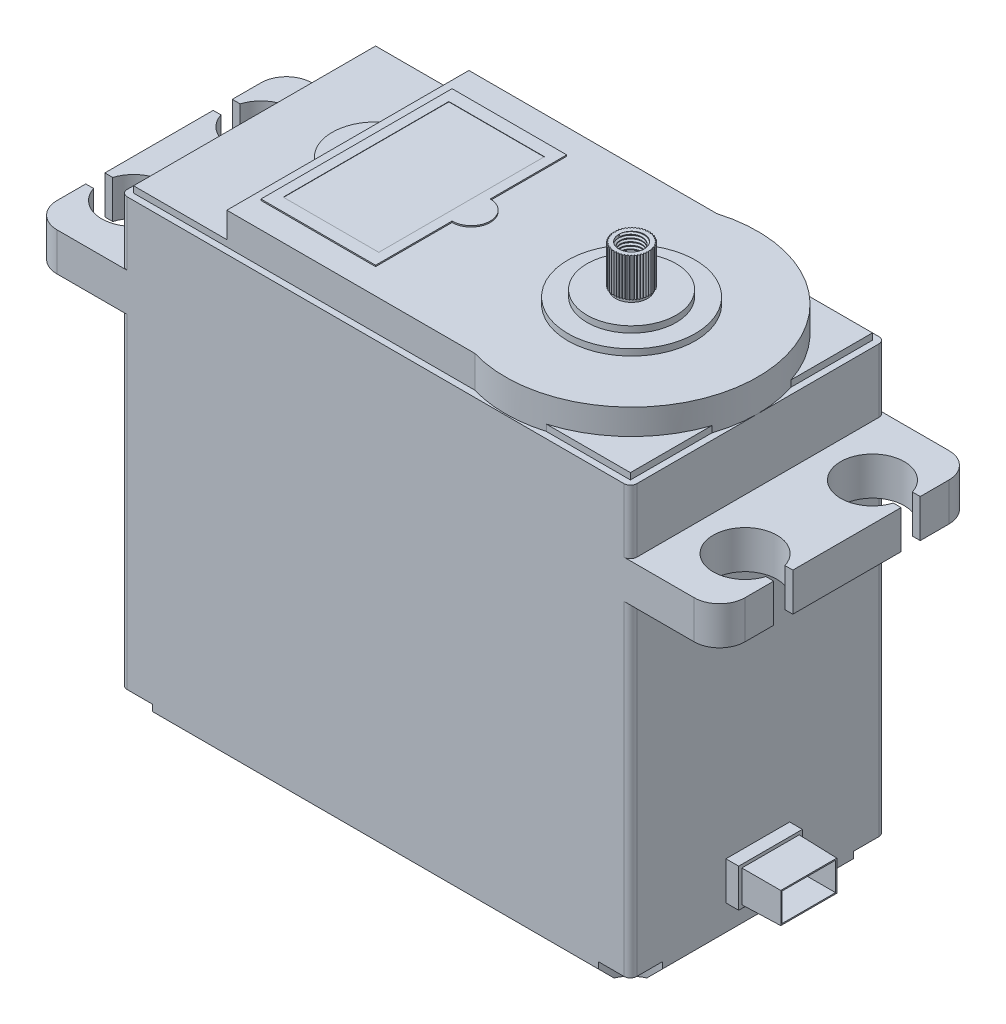
SolidWorks part; units mm, degrees
note: The reader was unsure of these and kept them because the rebuilt part matched: shared geometry of "Sketch11<4>", "Sketch11<5>", "Sketch11<6>".
material "ABS"
ref_plane "Front Plane" through (0, 0, 0) normal (0, 0, 1) x (1, 0, 0)
ref_plane "Top Plane" through (0, 0, 0) normal (0, 1, 0) x (1, 0, 0)
ref_plane "Right Plane" through (0, 0, 0) normal (1, 0, 0) x (0, 0, -1)
sketch "Sketch1" plane through (0, 0, 0) normal (0, 1, 0) x (1, 0, 0)
  line L1 (-20, -10) -> (20, -10)
  line L2 (-20, -10) -> (-20, 10)
  line L3 (-20, 10) -> (20, 10)
  line L4 (20, -10) -> (20, 10)
  line L5 (-20, -10) -> (20, 10) construction
  line L6 (-20, 10) -> (20, -10) construction
  point P0 (0, 0)
  dimension "D1" = 40
  dimension "D2" = 20
extrude "Boss-Extrude1" add sketch "Sketch1" along normal blind 35
sketch "Sketch2" plane through (20, 0, 0) normal (1, 0, 0) x (0, 0, -1)
  line L0 (-10, 35) -> (-10, 0) construction
  line L1 (-10, 30) -> (10, 30)
  line L2 (-10, 30) -> (-10, 27)
  line L3 (-10, 27) -> (10, 27)
  line L4 (10, 30) -> (10, 27)
  line L5 (10, 35) -> (10, 0) construction
  line L6 (-10, 35) -> (10, 35) construction
  dimension "D1" = 5
  dimension "D2" = 3
extrude "Boss-Extrude2" add sketch "Sketch2" along normal blind 7
sketch "Sketch3" plane through (0, 30, 0) normal (0, 1, 0) x (1, 0, 0)
  line L0 (30.4327, 0) -> (4.9254, 0) construction
  line L1 (0, 13.3538) -> (0, -14.6292) construction
  line L2 (26.3848, 5.75) -> (27, 5.75)
  line L3 (27, 10) -> (27, -10) construction
  line L4 (27, 5.75) -> (27, 4.25)
  line L5 (27, 4.25) -> (26.3848, 4.25)
  line L6 (27, -4.25) -> (26.3848, -4.25)
  line L7 (27, -5.75) -> (27, -4.25)
  line L8 (26.3848, -5.75) -> (27, -5.75)
  line L9 (-26.3848, -5.75) -> (-27, -5.75)
  line L10 (-27, -5.75) -> (-27, -4.25)
  line L11 (-27, -4.25) -> (-26.3848, -4.25)
  line L12 (-27, 4.25) -> (-26.3848, 4.25)
  line L13 (-27, 5.75) -> (-27, 4.25)
  line L14 (-26.3848, 5.75) -> (-27, 5.75)
  circle A0 centre (24, 5) radius 2.5
  circle A1 centre (24, -5) radius 2.5
  circle A2 centre (-24, -5) radius 2.5
  circle A3 centre (-24, 5) radius 2.5
  point P15 (27, 5)
  line M4 (27, -10) -> (27, 10)
  dimension "D2" = 5
  dimension "D1" = 10
  dimension "D3" = 1.5
  dimension "D4" = 3
sketch "Sketch4" plane through (-20, 0, 0) normal (-1, 0, 0) x (0, 0, 1)
  line L0 (10, 35) -> (10, 0) construction
  line L1 (-10, 30) -> (10, 30)
  line L2 (-10, 30) -> (-10, 27)
  line L3 (-10, 27) -> (10, 27)
  line L4 (10, 30) -> (10, 27)
  dimension "D1" = 3
extrude "Boss-Extrude3" add sketch "Sketch4" along normal blind 7
extrude "Cut-Extrude1" cut sketch "Sketch3" against normal through all contours A2 | A1 | A0 | A3 | A2 L11 L10 L9 | L12 A3 L14 L13 | L6 A1 L8 M4 | A0 L5 L2 M4
sketch "Sketch5" plane through (20, 0, 0) normal (1, 0, 0) x (0, 0, -1)
  line L0 (-10, 0) -> (10, 0) construction
  line L1 (-2.5, 6) -> (2.5, 6)
  line L2 (-2.5, 6) -> (-2.5, 3)
  line L3 (-2.5, 3) -> (2.5, 3)
  line L4 (2.5, 6) -> (2.5, 3)
  point P6 (0, 3)
  dimension "D1" = 5
  dimension "D2" = 3
  dimension "D3" = 3
extrude "Boss-Extrude4" add sketch "Sketch5" along normal blind 1
sketch "Sketch6" plane through (21, 0, 0) normal (1, 0, 0) x (0, 0, -1)
  line L0 (-2.5, 3) -> (2.5, 3) construction
  line L1 (-2.25, 5.75) -> (2.25, 5.75)
  line L2 (-2.25, 5.75) -> (-2.25, 3.25)
  line L3 (-2.25, 3.25) -> (2.25, 3.25)
  line L4 (2.25, 5.75) -> (2.25, 3.25)
  line L5 (2.5, 3) -> (2.5, 6) construction
  line L6 (-2.05, 5.55) -> (2.05, 5.55)
  line L7 (2.05, 5.55) -> (2.05, 3.45)
  line L8 (-2.05, 3.45) -> (2.05, 3.45)
  line L9 (-2.05, 5.55) -> (-2.05, 3.45)
  point P4 (0, 3.25)
  point P7 (0, 3)
  point P8 (2.25, 4.5)
  point P11 (2.5, 4.5)
  dimension "D1" = 4.5
  dimension "D2" = 2.5
  dimension "D3" = 0.2
extrude "Boss-Extrude5" add sketch "Sketch6" along normal blind 3 draft 1
sketch "Sketch10" plane through (0, 35, 0) normal (0, 1, 0) x (1, 0, 0)
  line L0 (-20, -10) -> (20, -10) construction
  line L1 (-19.5, 9.5) -> (19.5, 9.5)
  line L2 (-19.5, 9.5) -> (-19.5, -9.5)
  line L3 (-19.5, -9.5) -> (19.5, -9.5)
  line L4 (19.5, 9.5) -> (19.5, -9.5)
  line L5 (20, -10) -> (20, 10) construction
  point P4 (0, -9.5)
  point P6 (19.5, 0)
  dimension "D1" = 0.5
  dimension "D2" = 0.5
extrude "Boss-Extrude6" add sketch "Sketch10" along normal blind 0.5
sketch "Sketch11" plane through (0, 35.5, 0) normal (0, 1, 0) x (1, 0, 0)
  line L1 (-19.5, -9.5) -> (19.5, -9.5) construction
  line L4 (-12.1768, -9.5) -> (7.2877, -9.5)
  line L6 (-12.1768, 9.5) -> (-12.1768, -9.5)
  line L7 (7.2877, 9.5) -> (-12.1768, 9.5)
  arc A0 (7.2877, -9.5) -> (7.2877, 9.5) centre (10.0941, 0) ccw
  arc A1 (-12.1768, 2.8483) -> (-12.1768, -2.5749) centre (-10.1595, 0.1367) ccw
  circle A2 centre (10.0941, 0) radius 5
  circle A3 centre (10.0941, 0) radius 3.5
  circle A4 centre (10.0941, 0) radius 1.1906
  line M2 (-19.5, -9.5) -> (19.5, -9.5)
  line M3 (19.5, -9.5) -> (19.5, 9.5)
  line M4 (19.5, 9.5) -> (-19.5, 9.5)
  dimension "D1" = 7
  dimension "D2" = 10
extrude "Boss-Extrude7" add sketch "Sketch11" along normal blind 2 contours A0 L6 A2 M2 M3 M4 | A3 | A2 A3 | A0 M2 | A0 M3 | A0 M4
extrude "Boss-Extrude8" add sketch "Sketch11<4>" along normal blind 1.8 contours L6 A1
sketch "Sketch11<4>" plane through (0, 35.5, 0) normal (0, 1, 0) x (1, 0, 0) same geometry as "Sketch11"
sketch "Sketch12" plane through (0, 35.5, 0) normal (0, -1, 0) x (1, 0, 0)
  line L0 (7.2877, 9.5) -> (12.9006, 9.5) construction
  line L1 (7.2877, 9.5) -> (12.9006, 9.5)
  arc A0 (12.9006, 9.5) -> (7.2877, 9.5) centre (10.0941, 0) ccw construction
  arc A1 (12.9006, 9.5) -> (7.2877, 9.5) centre (10.0941, 0) ccw
extrude "Boss-Extrude9" add sketch "Sketch12" along normal up to next
sketch "Sketch13" plane through (0, 35.5, 0) normal (0, -1, 0) x (1, 0, 0)
  line L0 (19.5, 3.1074) -> (19.5, -3.1074) construction
  line L1 (19.5, 3.1074) -> (19.5, -3.1074)
  arc A0 (19.5, -3.1074) -> (19.5, 3.1074) centre (10.0941, 0) ccw construction
  arc A1 (19.5, -3.1074) -> (19.5, 3.1074) centre (10.0941, 0) ccw
extrude "Boss-Extrude10" add sketch "Sketch13" along normal up to next
sketch "Sketch14" plane through (0, 35.5, 0) normal (0, -1, 0) x (1, 0, 0)
  line L0 (12.9006, -9.5) -> (7.2877, -9.5) construction
  line L1 (12.9006, -9.5) -> (7.2877, -9.5)
  arc A0 (7.2877, -9.5) -> (12.9006, -9.5) centre (10.0941, 0) ccw construction
  arc A1 (7.2877, -9.5) -> (12.9006, -9.5) centre (10.0941, 0) ccw
extrude "Boss-Extrude11" add sketch "Sketch14" along normal up to next
extrude "Boss-Extrude12" add sketch "Sketch11<5>" along normal blind 2.5 and the other way blind 10 contours A2 A3 | A3
sketch "Sketch11<5>" plane through (0, 35.5, 0) normal (0, 1, 0) x (1, 0, 0) same geometry as "Sketch11"
extrude "Boss-Extrude13" add sketch "Sketch11<6>" along normal blind 3 contours A3
sketch "Sketch11<6>" plane through (0, 35.5, 0) normal (0, 1, 0) x (1, 0, 0) same geometry as "Sketch11"
sketch "Sketch16" plane through (0, 38.5, 0) normal (0, 1, 0) x (1, 0, 0)
  circle A0 centre (10.0941, 0) radius 1.25
  dimension "D1" = 2.5
extrude "Boss-Extrude14" add sketch "Sketch16" along normal blind 0.25
sketch "Sketch17" plane through (0, 38.75, 0) normal (0, 1, 0) x (1, 0, 0)
  line L0 (10.0941, 1.811) -> (10.0941, -2.1215) construction
  line L1 (10.2002, 1.396) -> (10.0941, 1.2899)
  line L2 (9.9881, 1.396) -> (10.0941, 1.2899)
  line L3 (10.1834, 1.3972) -> (10.2737, 1.2774)
  line L4 (10.3935, 1.3676) -> (10.2737, 1.2774)
  line L5 (10.377, 1.3711) -> (10.4497, 1.2399)
  line L6 (10.5809, 1.3127) -> (10.4497, 1.2399)
  line L7 (10.565, 1.3184) -> (10.6188, 1.1784)
  line L8 (10.7588, 1.2321) -> (10.6188, 1.1784)
  line L9 (10.7439, 1.2401) -> (10.7777, 1.0939)
  line L10 (10.9238, 1.1276) -> (10.7777, 1.0939)
  line L11 (10.9102, 1.1376) -> (10.9233, 0.9881)
  line L12 (11.0727, 1.0012) -> (10.9233, 0.9881)
  line L13 (11.0606, 1.0129) -> (11.0527, 0.8631)
  line L14 (11.2025, 0.8553) -> (11.0527, 0.8631)
  line L15 (11.1921, 0.8686) -> (11.1635, 0.7213)
  line L16 (11.3108, 0.6927) -> (11.1635, 0.7213)
  line L17 (11.3023, 0.7073) -> (11.2535, 0.5655)
  line L18 (11.3953, 0.5166) -> (11.2535, 0.5655)
  line L19 (11.389, 0.5323) -> (11.3209, 0.3986)
  line L20 (11.4546, 0.3305) -> (11.3209, 0.3986)
  line L21 (11.4505, 0.3469) -> (11.3645, 0.224)
  line L22 (11.4873, 0.138) -> (11.3645, 0.224)
  line L23 (11.4856, 0.1547) -> (11.3833, 0.045)
  line L24 (11.493, -0.0573) -> (11.3833, 0.045)
  line L25 (11.4936, -0.0404) -> (11.377, -0.1348)
  line L26 (11.4714, -0.2514) -> (11.377, -0.1348)
  line L27 (11.4743, -0.2348) -> (11.3457, -0.3121)
  line L28 (11.423, -0.4406) -> (11.3457, -0.3121)
  line L29 (11.4282, -0.4246) -> (11.2901, -0.4832)
  line L30 (11.3487, -0.6213) -> (11.2901, -0.4832)
  line L31 (11.3561, -0.6061) -> (11.2112, -0.645)
  line L32 (11.2501, -0.7898) -> (11.2112, -0.645)
  line L33 (11.2595, -0.7759) -> (11.1106, -0.7941)
  line L34 (11.1289, -0.943) -> (11.1106, -0.7941)
  line L35 (11.1402, -0.9305) -> (10.9902, -0.9279)
  line L36 (10.9876, -1.0779) -> (10.9902, -0.9279)
  line L37 (11.0005, -1.067) -> (10.8523, -1.0436)
  line L38 (10.8289, -1.1917) -> (10.8523, -1.0436)
  line L39 (10.8432, -1.1828) -> (10.6997, -1.1389)
  line L40 (10.6559, -1.2824) -> (10.6997, -1.1389)
  line L41 (10.6713, -1.2755) -> (10.5353, -1.2121)
  line L42 (10.4719, -1.3481) -> (10.5353, -1.2121)
  line L43 (10.4881, -1.3434) -> (10.3623, -1.2617)
  line L44 (10.2806, -1.3875) -> (10.3623, -1.2617)
  line L45 (10.2973, -1.3852) -> (10.1841, -1.2868)
  line L46 (10.0857, -1.4) -> (10.1841, -1.2868)
  line L47 (10.1026, -1.4) -> (10.0042, -1.2868)
  line L48 (9.891, -1.3852) -> (10.0042, -1.2868)
  line L49 (9.9076, -1.3875) -> (9.826, -1.2617)
  line L50 (9.7002, -1.3434) -> (9.826, -1.2617)
  line L51 (9.7164, -1.3481) -> (9.653, -1.2121)
  line L52 (9.517, -1.2755) -> (9.653, -1.2121)
  line L53 (9.5324, -1.2824) -> (9.4886, -1.1389)
  line L54 (9.3451, -1.1828) -> (9.4886, -1.1389)
  line L55 (9.3594, -1.1917) -> (9.3359, -1.0436)
  line L56 (9.1878, -1.067) -> (9.3359, -1.0436)
  line L57 (9.2007, -1.0779) -> (9.1981, -0.9279)
  line L58 (9.0481, -0.9305) -> (9.1981, -0.9279)
  line L59 (9.0594, -0.943) -> (9.0777, -0.7941)
  line L60 (8.9288, -0.7759) -> (9.0777, -0.7941)
  line L61 (8.9382, -0.7898) -> (8.977, -0.645)
  line L62 (8.8322, -0.6061) -> (8.977, -0.645)
  line L63 (8.8395, -0.6213) -> (8.8982, -0.4832)
  line L64 (8.7601, -0.4246) -> (8.8982, -0.4832)
  line L65 (8.7653, -0.4406) -> (8.8425, -0.3121)
  line L66 (8.714, -0.2348) -> (8.8425, -0.3121)
  line L67 (8.7169, -0.2514) -> (8.8113, -0.1348)
  line L68 (8.6947, -0.0404) -> (8.8113, -0.1348)
  line L69 (8.6953, -0.0573) -> (8.805, 0.045)
  line L70 (8.7027, 0.1547) -> (8.805, 0.045)
  line L71 (8.701, 0.138) -> (8.8238, 0.224)
  line L72 (8.7378, 0.3469) -> (8.8238, 0.224)
  line L73 (8.7337, 0.3305) -> (8.8674, 0.3986)
  line L74 (8.7993, 0.5323) -> (8.8674, 0.3986)
  line L75 (8.7929, 0.5166) -> (8.9348, 0.5655)
  line L76 (8.8859, 0.7073) -> (8.9348, 0.5655)
  line L77 (8.8775, 0.6927) -> (9.0248, 0.7213)
  line L78 (8.9961, 0.8686) -> (9.0248, 0.7213)
  line L79 (8.9858, 0.8553) -> (9.1355, 0.8631)
  line L80 (9.1277, 1.0129) -> (9.1355, 0.8631)
  line L81 (9.1156, 1.0012) -> (9.265, 0.9881)
  line L82 (9.2781, 1.1376) -> (9.265, 0.9881)
  line L83 (9.2644, 1.1276) -> (9.4106, 1.0939)
  line L84 (9.4443, 1.2401) -> (9.4106, 1.0939)
  line L85 (9.4294, 1.2321) -> (9.5695, 1.1784)
  line L86 (9.6232, 1.3184) -> (9.5695, 1.1784)
  line L87 (9.6074, 1.3127) -> (9.7386, 1.2399)
  line L88 (9.8113, 1.3711) -> (9.7386, 1.2399)
  line L89 (9.7948, 1.3676) -> (9.9146, 1.2774)
  line L90 (10.0049, 1.3972) -> (9.9146, 1.2774)
  circle A0 centre (10.0941, 0) radius 1.4
  point P143 (10.0941, 0)
  dimension "D1" = 2.8
  dimension "D2" = 45
  dimension "D3" = 0.15
  dimension "D4" = 45
extrude "Boss-Extrude17" add sketch "Sketch17" along normal blind 3 contours L0 L2 | L2 L0 | L1 L0 L2 L46 L45 L44 L43 L42 L41 L40 L39 L38 L37 L36 L35 L34 L33 L32 L31 L30 L29 L28 L27 L26 L25 L24 L23 L22 L21 L20 L19 L18 L17 L16 L15 L14 L13 L12 L11 L10 L9 L8 L7 L6 L5 L4 L3 | L0 L2 L90 L89 L88 L87 L86 L85 L84 L83 L82 L81 L80 L79 L78 L77 L76 L75 L74 L73 L72 L71 L70 L69 L68 L67 L66 L65 L64 L63 L62 L61 L60 L59 L58 L57 L56 L55 L54 L53 L52 L51 L50 L49 L48 L47
sketch "Sketch28" plane through (0, 41.75, 0) normal (0, 1, 0) x (1, 0, 0)
  circle A0 centre (10.0941, 0) radius 1
  dimension "D1" = 2
extrude "Cut-Extrude3" cut sketch "Sketch28" against normal blind 2.5
thread "Thread2" pitch 0.25 start angle 0, offset 0, length 0, pitch 0.25, diameter 2
ref_plane "Plane3" through (9.0941, 41.75, 0) normal (0, 0, 1) x (-1, 0, 0)
sketch "Thread Profile3" plane through (9.0941, 41.75, 0) normal (0, 0, 1) x (-1, 0, 0)
  line L0 (0, 0) -> (0, 0.25) construction
  line L11 (0, 0) -> (0, 0.2187)
  line L12 (0, 0.2187) -> (-0.1353, 0.1406)
  line L13 (-0.1353, 0.1406) -> (-0.1353, 0.0781)
  line L15 (-0.1353, 0.0781) -> (0, 0)
  line L17 (-0.1353, 0.1094) -> (0, 0.1094) construction
  point P2 (0, 0)
  dimension "Pitch" = 0.25
  dimension "Profile_Angle" = 60
  dimension "Profile_Land" = 0.0625
  dimension "Profile_Height" = 0.1353
sketch "Sketch29" plane through (0, 37.5, 0) normal (0, 1, 0) x (1, 0, 0)
  line L1 (-11.5, 7.5) -> (-2.5, 7.5)
  line L2 (-11.5, 7.5) -> (-11.5, -7.5)
  line L3 (-11.5, -7.5) -> (-2.5, -7.5)
  line L4 (-2.5, 7.5) -> (-2.5, 1.5)
  line L5 (-2.5, -1.5) -> (-2.5, -7.5)
  arc A0 (-2.5, -1.5) -> (-2.5, 1.5) centre (-2.5, 0) ccw
  point P8 (-11.5, 0)
  dimension "D4" = 3
  dimension "D1" = 9
  dimension "D2" = 15
  dimension "D3" = 2.5
extrude "Boss-Extrude18" add sketch "Sketch29" along normal blind 0.1
sketch "Sketch30" plane through (0, 37.6, 0) normal (0, 1, 0) x (1, 0, 0)
  line L0 (-2.5, 7.5) -> (-11.5, 7.5) construction
  line L1 (-10.75, 6.5) -> (-3.25, 6.5)
  line L2 (-10.75, 6.5) -> (-10.75, -6.5)
  line L3 (-10.75, -6.5) -> (-3.25, -6.5)
  line L4 (-3.25, 6.5) -> (-3.25, -6.5)
  point P4 (-10.75, 0)
  point P8 (-7, 7.5)
  point P9 (-7, 6.5)
  dimension "D1" = 7.5
  dimension "D2" = 13
extrude "Cut-Extrude4" cut sketch "Sketch30" against normal blind 0.025
fillet "Fillet2" radius 2 4 edges at (-27, 28.5, 10) (-27, 28.5, -10) (27, 28.5, -10) (27, 28.5, 10)
sketch "Sketch31" plane through (0, 0, 0) normal (0, -1, 0) x (1, 0, 0)
  line L0 (20, 10) -> (20, -10) construction
  line L1 (20, -10) -> (-20, -10) construction
  line L2 (-20, -10) -> (-20, 10) construction
  line L3 (-20, 10) -> (20, 10) construction
  line L4 (20, 10) -> (20, 7.5)
  line L5 (20, -10) -> (17.5, -10)
  line L6 (-20, -10) -> (-20, -7.5)
  line L7 (-20, 10) -> (-17.5, 10)
  line L8 (17.5, 10) -> (20, 10)
  line L9 (-17.5, -10) -> (-20, -10)
  line L10 (-20, 7.5) -> (-20, 10)
  line L11 (20, -7.5) -> (20, -10)
  arc A0 (-20, 7.5) -> (-17.5, 10) centre (-20, 10) ccw
  arc A1 (17.5, 10) -> (20, 7.5) centre (20, 10) ccw
  arc A2 (20, -7.5) -> (17.5, -10) centre (20, -10) ccw
  arc A3 (-17.5, -10) -> (-20, -7.5) centre (-20, -10) ccw
  dimension "D1" = 5
extrude "Cut-Extrude5" cut sketch "Sketch31" against normal blind 1.5
hole_wizard "M1.2x0.25 Tapped Hole1" positions "Sketch32" profile "Sketch33" tap size "M1.2x0.25" standard "ANSI Metric"
sketch "Sketch32" plane through (0, 1.5, 0) normal (0, -1, 0) x (-1, 0, 0)
  point P0 (18.9615, -8.994)
  point P2 (18.9615, 8.9745)
  point P4 (-18.8958, 8.9745)
  point P6 (-18.8958, -8.994)
cosmetic thread "Hole Thread1" parameters "D1"=30, "D2"=1.2
cosmetic thread "Hole Thread2" parameters "D1"=30, "D2"=1.2
cosmetic thread "Hole Thread3" parameters "D1"=30, "D2"=1.2
cosmetic thread "Hole Thread4" parameters "D1"=30, "D2"=1.2
sketch "Sketch33" plane through (-18.9615, 1.5, 8.994) normal (1, 0, 0) x (0, 0, -1)
  line L0 (0, 0) -> (0, 30.2854)
  line L1 (0, 30.2854) -> (0.475, 30)
  line L2 (0.475, 30) -> (0.475, 0.15)
  line L3 (0.475, 0.15) -> (0.625, 0)
  line L5 (0.625, 0) -> (0, 0)
  line L6 (-0.475, 0.15) -> (-0.625, 0) construction
  line L10 (0, 30.2854) -> (-0.475, 30) construction
  line L11 (0, -6.35) -> (0, 107.95) construction
  dimension "Tap Drill Dia." = 0.95
  dimension "Tap Drill Depth" = 30
  dimension "Near C'Sink Dia." = 1.25
  dimension "Near C'Sink Angle" = 90
  dimension "Drill Angle" = 118
fillet "Fillet3" radius 0.5 8 edges at (20, 32.5, -10) (20, 14.25, -10) (20, 32.5, 10) (20, 14.25, 10) (-20, 32.5, 10) (-20, 32.5, -10) (-20, 14.25, -10) (-20, 14.25, 10)
chamfer "Chamfer1" distance 1 angle 45 4 edges at (20, 0, 0) (0, 0, -10) (0, 0, 10) (-20, 0, 0)
sketch "Sketch35" plane through (0, 27, 0) normal (0, -1, 0) x (1, 0, 0)
  line L0 (-37.5796, 0) -> (35.24, 0) construction
  line L1 (-25.7232, 1.7258) -> (-25.7232, -1.7258)
  line L2 (-20.8194, 3.1096) -> (-20.8194, -3.1096)
  line L3 (0, 15.108) -> (0, -19.0701) construction
  line L4 (20.8194, 3.1096) -> (20.8194, -3.1096)
  line L5 (25.7232, 1.7258) -> (25.7232, -1.7258)
  arc A1 (-20.8194, 3.1096) -> (-25.7232, 1.7258) centre (-24, 5) cw
  arc A2 (-20.8194, -3.1096) -> (-25.7232, -1.7258) centre (-24, -5) ccw
  arc A3 (20.8194, -3.1096) -> (25.7232, -1.7258) centre (24, -5) cw
  arc A4 (20.8194, 3.1096) -> (25.7232, 1.7258) centre (24, 5) ccw
  point P6 (-25.7232, 0)
  point P12 (-20.8194, 0)
  point P19 (20.8194, 0)
  point P20 (25.7232, 0)
extrude "Cut-Extrude6" cut sketch "Sketch35" against normal blind 1.5
ref_plane "Plan1" through (-27, 30, 4.25) normal (0, 0, -1) x (-1, 0, 0)
